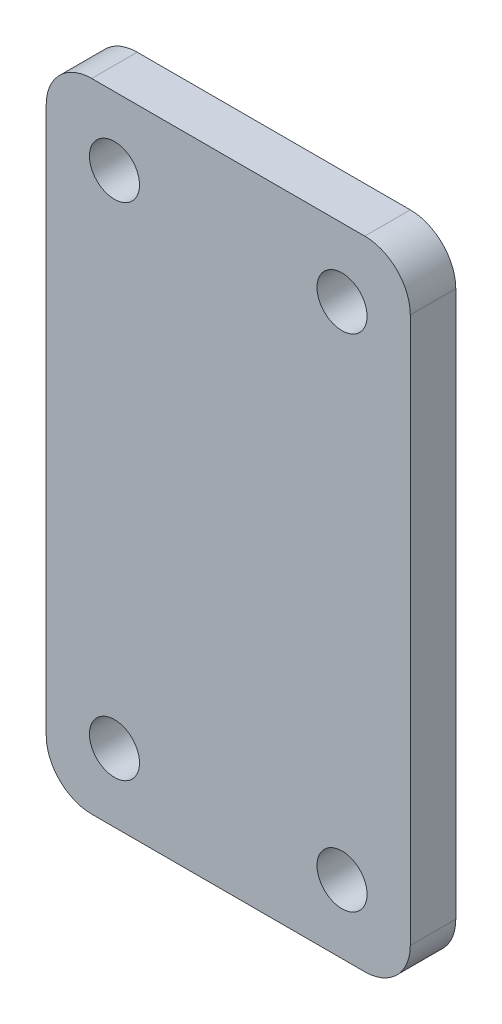
SolidWorks part; units mm, degrees
material "1.4003 (X2CrNi12)"
ref_plane "Ön Düzlem" through (0, 0, 0) normal (0, 0, 1) x (1, 0, 0)
ref_plane "Üst Düzlem" through (0, 0, 0) normal (0, 1, 0) x (1, 0, 0)
ref_plane "Sağ Düzlem" through (0, 0, 0) normal (1, 0, 0) x (0, 0, -1)
sketch "Çizim1" plane through (0, 0, 0) normal (0, 0, 1) x (1, 0, 0)
  line L1 (-40, 70) -> (40, 70)
  line L2 (-40, 70) -> (-40, -70)
  line L3 (-40, -70) -> (40, -70)
  line L4 (40, 70) -> (40, -70)
  line L5 (-40, 70) -> (40, -70) construction
  line L6 (-40, -70) -> (40, 70) construction
  point P0 (0, 0)
  dimension "D1" = 80
  dimension "D2" = 140
base flange "Taban-Flanş1" sketch "Çizim1" thickness 10 reverse thickness direction no parameters "D1"=5
fillet "Radyus1" radius 10 4 edges at (-40, 70, -5) (40, 70, -5) (40, -70, -5) (-40, -70, -5)
sketch "Çizim2" plane through (0, 0, 0) normal (0, 0, 1) x (1, 0, 0)
  line L1 (-25, 55) -> (25, 55) construction
  line L2 (-25, 55) -> (-25, -55) construction
  line L3 (-25, -55) -> (25, -55) construction
  line L4 (25, 55) -> (25, -55) construction
  line L5 (-25, 55) -> (25, -55) construction
  line L6 (-25, -55) -> (25, 55) construction
  circle A0 centre (25, 55) radius 5.5
  circle A1 centre (-25, 55) radius 5.5
  circle A2 centre (-25, -55) radius 5.5
  circle A3 centre (25, -55) radius 5.5
  point P0 (0, 0)
  dimension "D3" = 11
  dimension "D1" = 50
  dimension "D2" = 110
extrude "Kes-Ekstrüzyon1" cut sketch "Çizim2" against normal blind 20
sketch "Büküm-Çizgileri1" [suppressed] plane through (0, 0, 0) normal (0, 1, 0) x (1, 0, 0)
sketch "Sınırlandırma-Kutusu1" [suppressed] plane through (0, 0, 0) normal (0, 1, 0) x (1, 0, 0)
sheet metal parameters "Sac-Levha1" thickness 10 parameters "D1"=5
flat pattern "Düz-Çoğaltma1" [suppressed]
sketch "Büküm-Çizgileri2" plane through (0, 0, 0) normal (0, 1, 0) x (1, 0, 0)
sketch3d "Sınırlandırma-Kutusu2" [suppressed]
  line L0 (40, 70, 0) -> (40, -70, 0) construction
  line L1 (-40, 70, 0) -> (-40, -70, 0) construction
  line L2 (40, 70, 0) -> (-40, 70, 0) construction
  line L3 (40, -70, 0) -> (-40, -70, 0) construction
sheet metal parameters "Sac-Levha2" thickness 10 parameters "D1"=5
flat pattern "Düz-Çoğaltma1"
sketch "Büküm-Çizgileri2" plane through (0, 0, 0) normal (0, 1, 0) x (1, 0, 0)
sketch3d "Sınırlandırma-Kutusu2" [suppressed]
  line L0 (40, 70, 0) -> (40, -70, 0) construction
  line L1 (-40, 70, 0) -> (-40, -70, 0) construction
  line L2 (40, 70, 0) -> (-40, 70, 0) construction
  line L3 (40, -70, 0) -> (-40, -70, 0) construction
